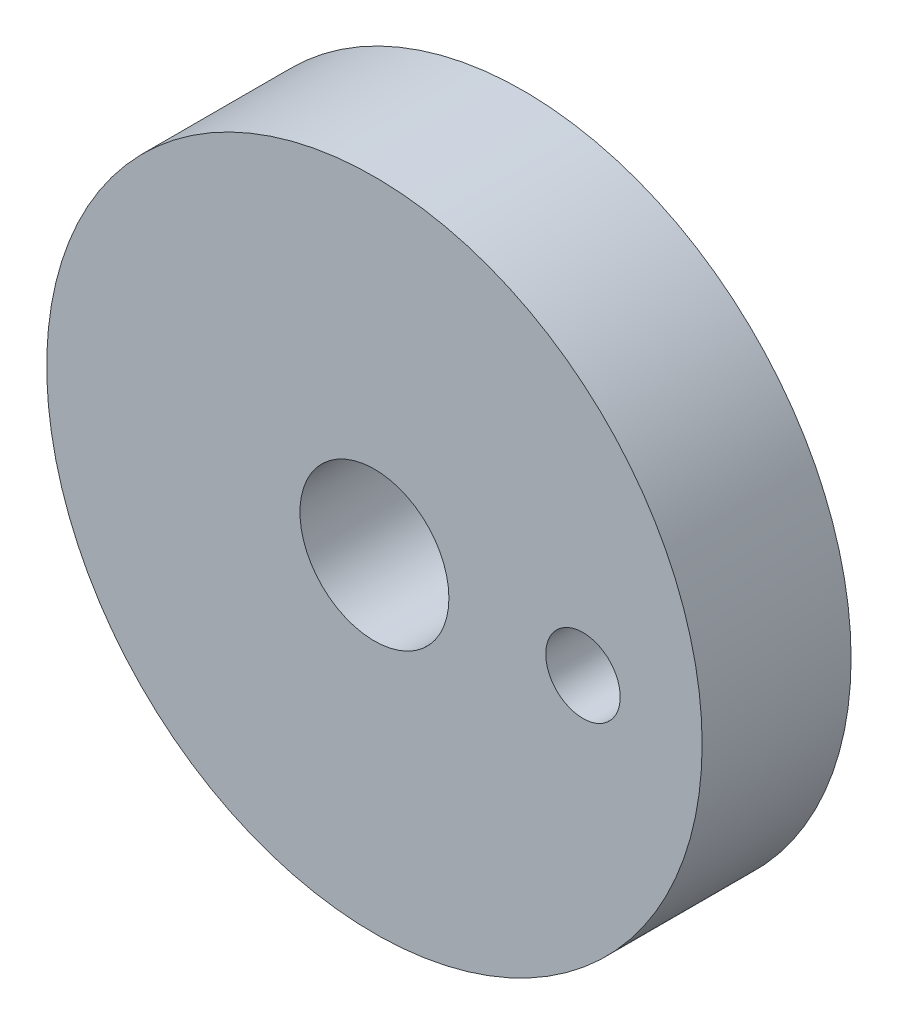
SolidWorks part; units mm, degrees
ref_plane "Front Plane" through (0, 0, 0) normal (0, 0, 1) x (1, 0, 0)
ref_plane "Top Plane" through (0, 0, 0) normal (0, 1, 0) x (1, 0, 0)
ref_plane "Right Plane" through (0, 0, 0) normal (1, 0, 0) x (0, 0, -1)
sketch "Sketch1" plane through (0, 0, 0) normal (0, 0, 1) x (1, 0, 0)
  circle A0 centre (0, 0) radius 13.97
  dimension "D1" = 27.94
extrude "Boss-Extrude1" add sketch "Sketch1" along normal blind 6.35 contours A0 | A0 | A0 region at (0, 0, 0)
sketch "Sketch2" plane through (0, 0, 6.35) normal (0, 0, 1) x (1, 0, 0)
  circle A0 centre (8.89, 0) radius 1.5875
  circle A2 centre (0, 0) radius 3.175
  dimension "D1" = 3.175
  dimension "D2" = 8.89
  dimension "D3" = 6.35
extrude "Cut-Extrude1" cut sketch "Sketch2" against normal through all
